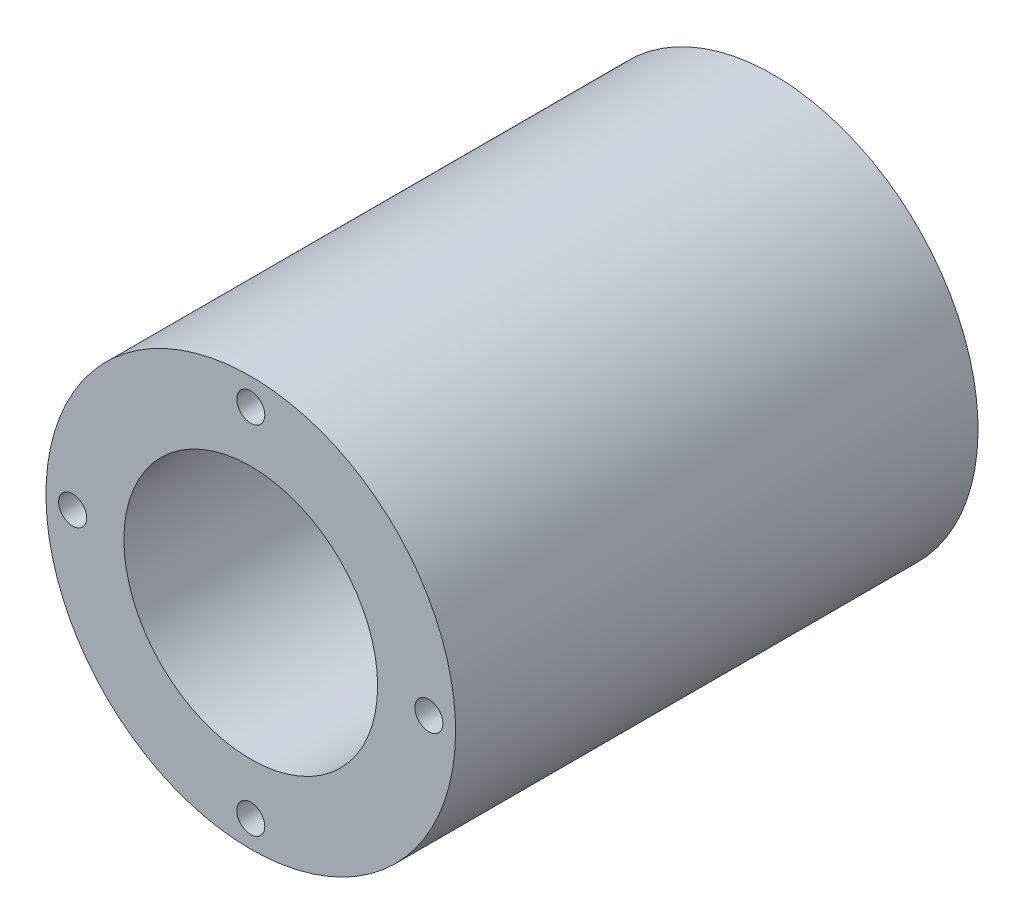
SolidWorks part; units mm, degrees
material "6061-T6 (SS)"
ref_plane "Front Plane" through (0, 0, 0) normal (0, 0, 1) x (1, 0, 0)
ref_plane "Top Plane" through (0, 0, 0) normal (0, 1, 0) x (1, 0, 0)
ref_plane "Right Plane" through (0, 0, 0) normal (1, 0, 0) x (0, 0, -1)
sketch "Sketch Spindle Skeleton" plane through (0, 0, 0) normal (1, 0, 0) x (0, 0, -1)
  line L0 (-95.847, -9.525) -> (-140.95, -9.525)
  line L5 (-1000, 0) -> (49000, 0)
  line L6 (0, -9.525) -> (0, 9.525)
  line L13 (0, 9.525) -> (-45.847, 9.525)
  line L26 (-45.847, 9.525) -> (-45.847, 14)
  line L27 (-45.847, 14) -> (-95.847, 14)
  line L32 (-95.847, 14) -> (-95.847, 9.525)
  line L34 (-160, 7) -> (-160, -7)
  line L36 (-95.847, -9.525) -> (-95.847, -14)
  line L37 (-95.847, -14) -> (-45.847, -14)
  line L38 (-45.847, -14) -> (-45.847, -9.525)
  line L39 (0, -9.525) -> (-45.847, -9.525)
  line L40 (-26.321, 36.5125) -> (-17.321, 36.5125)
  line L41 (-111.341, 22.6187) -> (-95.847, 22.6187)
  line L42 (-111.341, 22.6187) -> (-111.341, -22.6187)
  line L43 (-111.341, -22.6187) -> (-95.847, -22.6187)
  line L44 (-95.847, 22.6187) -> (-95.847, -22.6187)
  line L45 (-111.341, 22.6187) -> (-95.847, -22.6187) construction
  line L46 (-111.341, -22.6187) -> (-95.847, 22.6187) construction
  line L47 (-30.353, 22.6187) -> (-45.847, 22.6187)
  line L48 (-30.353, 22.6187) -> (-30.353, -22.6187)
  line L49 (-30.353, -22.6187) -> (-45.847, -22.6187)
  line L50 (-45.847, 22.6187) -> (-45.847, -22.6187)
  line L51 (-30.353, 22.6187) -> (-45.847, -22.6187) construction
  line L52 (-30.353, -22.6187) -> (-45.847, 22.6187) construction
  line L59 (-17.321, 36.5125) -> (-17.321, -36.5125)
  line L60 (-17.321, -36.5125) -> (-26.321, -36.5125)
  line L61 (-26.321, -22.6187) -> (-28.321, -22.6187)
  line L62 (-28.321, -22.6187) -> (-28.321, -12.5)
  line L63 (-28.321, -12.5) -> (-26.321, -12.5)
  line L64 (-26.321, -12.5) -> (-26.321, 12.5)
  line L65 (-26.321, 12.5) -> (-28.321, 12.5)
  line L66 (-28.321, 12.5) -> (-28.321, 22.6187)
  line L67 (-28.321, 22.6187) -> (-26.321, 22.6187)
  line L68 (-26.321, 22.6187) -> (-26.321, 36.5125)
  line L69 (-26.321, -22.6187) -> (-26.321, -36.5125)
  line L71 (-119.469, 36.5125) -> (-26.321, 36.5125)
  line L72 (-119.469, 36.5125) -> (-119.469, -36.5125)
  line L73 (-119.469, -36.5125) -> (-26.321, -36.5125)
  line L74 (-26.321, 36.5125) -> (-26.321, -36.5125)
  line L75 (-119.469, 36.5125) -> (-26.321, -36.5125) construction
  line L76 (-119.469, -36.5125) -> (-26.321, 36.5125) construction
  line L77 (-140.95, -9.525) -> (-140.95, -7)
  line L78 (-140.95, -7) -> (-160, -7)
  line L79 (-95.847, 9.525) -> (-140.95, 9.525)
  line L80 (-140.95, 7) -> (-160, 7)
  line L81 (-140.95, 9.525) -> (-140.95, 7)
  line L82 (-118.3985, 9.525) -> (-118.3985, -9.525) construction
  line L83 (-22.9235, 9.525) -> (-22.9235, -9.525) construction
  line L96 (-119.469, 36.5125) -> (-134.709, 36.5125)
  line L98 (-119.469, -36.5125) -> (-134.709, -36.5125)
  line L99 (-134.709, 36.5125) -> (-134.709, -36.5125)
  line L110 (-119.469, 36.5125) -> (-119.469, -36.5125)
  point P3 (0, 0)
  point P18 (-103.594, 0)
  point P24 (-38.1, 0)
  point P29 (-72.895, 0)
  point P48 (-17.321, 30.5656)
  point P70 (-134.709, 31.75)
sketch "Sketch1" plane through (0, 0, 0) normal (1, 0, 0) x (0, 0, -1)
  line L0 (-26.321, 36.5125) -> (-26.321, -36.5125) construction
  line L1 (-119.469, -36.5125) -> (-26.321, -36.5125) construction
  line L2 (-119.469, 36.5125) -> (-119.469, -36.5125) construction
  line L3 (-119.469, 36.5125) -> (-26.321, 36.5125) construction
  line L4 (-26.321, 36.5125) -> (-26.321, -36.5125)
  line L5 (-119.469, -36.5125) -> (-26.321, -36.5125)
  line L6 (-119.469, 36.5125) -> (-119.469, -36.5125)
  line L7 (-119.469, 36.5125) -> (-26.321, 36.5125)
  line L9 (-30.353, 22.6187) -> (-45.847, 22.6187) construction
  line L10 (-119.469, 22.6187) -> (-26.321, 22.6187)
  line L15 (-119.469, 0) -> (-26.321, 0) construction
revolve "Revolve1" add sketch "Sketch1" angle 360 about L15 region at (0, 29.5656, 72.895)
sketch "Back Hole Top Location" plane through (0, 0, 26.321) normal (0, 0, -1) x (-1, 0, 0)
  point P9 (0, 30.5656)
hole_wizard "M6x1.0 Tapped Hole3" positions "Sketch8" profile "Sketch9" tap size "M6x1.0" standard "ANSI Metric"
sketch "Sketch8" plane through (0, 0, 26.321) normal (0, 0, -1) x (-1, 0, 0)
  point P0 (0, 30.5656)
sketch "Sketch9" plane through (0, 30.5656, 26.321) normal (1, 0, 0) x (0, 1, 0)
  line L0 (0, 0) -> (0, 16.5022)
  line L1 (0, 16.5022) -> (2.5, 15)
  line L2 (2.5, 15) -> (2.5, 0)
  line L5 (2.5, 0) -> (0, 0)
  line L10 (0, 16.5022) -> (-2.5, 15) construction
  line L11 (0, -6.35) -> (0, 107.95) construction
  dimension "Tap Drill Dia." = 5
  dimension "Tap Drill Depth" = 15
  dimension "Drill Angle" = 118
pattern_circular "BackFacePattern" count 6 over 360 about axis through (0, 0, 1000) along (0, 0, -1) of "M6x1.0 Tapped Hole3"
ref_plane "Midplane" through (0, 0, 72.895) normal (0, 0, -1) x (-1, 0, 0)
sketch "Front Hole Top Location" plane through (0, 0, 119.469) normal (0, 0, 1) x (1, 0, 0)
  point P0 (0, 31.75)
hole_wizard "M6x1.0 Tapped Hole2" positions "Sketch5" profile "Sketch6" tap size "M6x1.0" standard "ANSI Metric"
sketch "Sketch5" plane through (0, 0, 119.469) normal (0, 0, 1) x (1, 0, 0)
  point P0 (0, 31.75)
sketch "Sketch6" plane through (0, 31.75, 119.469) normal (1, 0, 0) x (0, -1, 0)
  line L0 (0, 0) -> (0, 16.5022)
  line L1 (0, 16.5022) -> (2.5, 15)
  line L2 (2.5, 15) -> (2.5, 0)
  line L5 (2.5, 0) -> (0, 0)
  line L10 (0, 16.5022) -> (-2.5, 15) construction
  line L11 (0, -6.35) -> (0, 107.95) construction
  dimension "Tap Drill Dia." = 5
  dimension "Tap Drill Depth" = 15
  dimension "Drill Angle" = 118
pattern_circular "FrontFacePattern" count 4 over 360 about axis through (0, 0, 1000) along (0, 0, -1) of "M6x1.0 Tapped Hole2"
sketch "Sketch7" plane through (0, 0, 26.321) normal (0, 0, -1) x (-1, 0, 0)
  circle A0 centre (0, 0) radius 26.9875
  circle A1 centre (0, 0) radius 24.6062
  dimension "D1" = 53.975
  dimension "D2" = 49.2125
extrude "Cut-Extrude1" [suppressed] cut sketch "Sketch7" against normal blind 0.5
